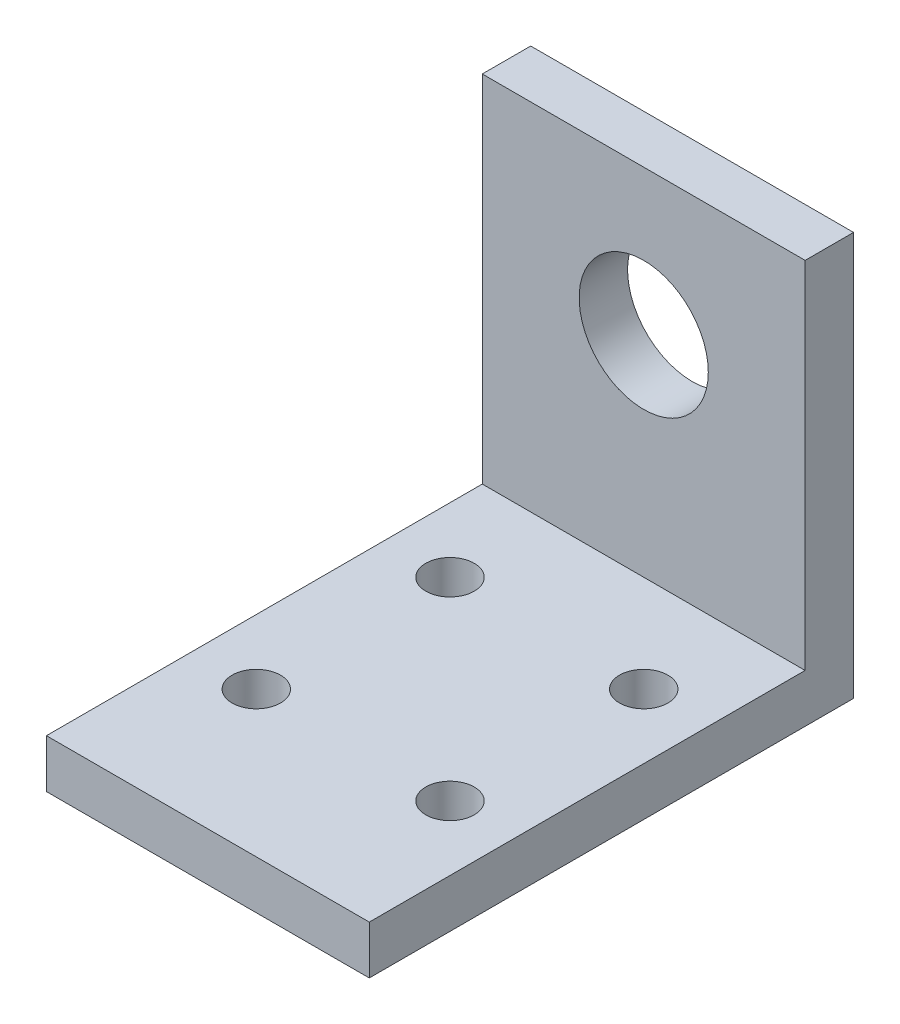
SolidWorks part; units mm, degrees
material "6063-O"
ref_plane "Front" through (0, 0, 0) normal (0, 0, 1) x (1, 0, 0)
ref_plane "Top" through (0, 0, 0) normal (0, 1, 0) x (1, 0, 0)
ref_plane "Right" through (0, 0, 0) normal (1, 0, 0) x (0, 0, -1)
sketch "草图1" plane through (0, 0, 0) normal (1, 0, 0) x (0, 0, -1)
  line L0 (0, 0) -> (0, 22)
  line L1 (0, 22) -> (3, 22)
  line L2 (3, 22) -> (3, -3)
  line L3 (3, -3) -> (-35, -3)
  line L4 (-35, -3) -> (-35, 0)
  line L5 (-35, 0) -> (0, 0)
  dimension "D1" = 22
  dimension "D2" = 3
  dimension "D3" = 25
  dimension "D4" = 38
extrude "凸台-拉伸1" add sketch "草图1" along normal blind 20
sketch "草图2" plane through (0, 0, 0) normal (0, 0, 1) x (1, 0, 0)
  line L0 (10, 22) -> (10, -3) construction
  line L1 (20, 22) -> (0, 22) construction
  line L2 (20, -3) -> (0, -3) construction
  circle A0 centre (10, 13) radius 4
  dimension "D1" = 8
  dimension "D2" = 9
extrude "切除-拉伸1" cut sketch "草图2" against normal up to next
sketch "草图3" plane through (0, 0, 0) normal (0, 1, 0) x (1, 0, 0)
  line L0 (10, 3) -> (10, -30.8482) construction
  line L1 (20, 3) -> (0, 3) construction
  circle A0 centre (4, -6) radius 1.5
  circle A1 centre (16, -6) radius 1.5
  dimension "D1" = 3
  dimension "D2" = 3
  dimension "D3" = 12
  dimension "D4" = 9
extrude "切除-拉伸2" cut sketch "草图3" against normal up to next
sketch "草图4" plane through (0, -3, 0) normal (0, -1, 0) x (1, 0, 0)
  line L0 (40, 27) -> (0, 27) construction
  line L1 (20, 27) -> (0, 27)
  line L2 (20, 27) -> (20, 35)
  line L3 (20, 35) -> (0, 35)
  line L4 (0, 27) -> (0, 35)
extrude "切除-拉伸3" cut sketch "草图4" against normal blind 10
sketch "草图5" plane through (0, -3, 0) normal (0, -1, 0) x (1, 0, 0)
  circle A0 centre (16, 18) radius 1.5
  circle A1 centre (4, 18) radius 1.5
extrude "切除-拉伸4" cut sketch "草图5" against normal blind 10
